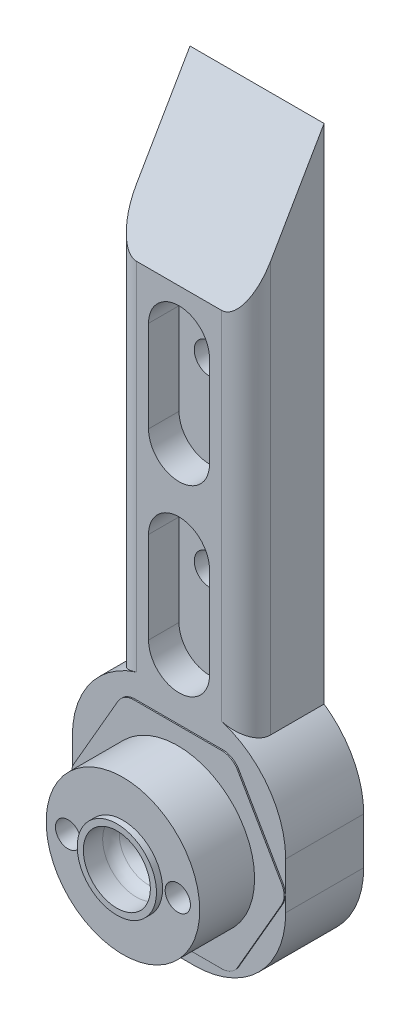
SolidWorks part; units mm, degrees
ref_plane "前视基准面" through (0, 0, 0) normal (0, 0, 1) x (1, 0, 0)
ref_plane "上视基准面" through (0, 0, 0) normal (0, 1, 0) x (1, 0, 0)
ref_plane "右视基准面" through (0, 0, 0) normal (1, 0, 0) x (0, 0, -1)
sketch "草图1" plane through (0, 0, 0) normal (0, 0, 1) x (1, 0, 0)
  circle A0 centre (0, 0) radius 12.6
  dimension "D1" = 25.2
extrude "凸台-拉伸1" add sketch "草图1" along normal blind 9
sketch "草图2" plane through (0, 0, 0) normal (0, 0, -1) x (-1, 0, 0)
  circle A0 centre (0, 0) radius 15
  dimension "D1" = 30
extrude "凸台-拉伸2" add sketch "草图2" along normal blind 5
sketch "草图3" plane through (0, 0, 9) normal (0, 0, 1) x (1, 0, 0)
  circle A0 centre (0, 0) radius 5.5
  dimension "D1" = 11
extrude "切除-拉伸1" cut sketch "草图3" against normal blind 5
sketch "草图4" plane through (0, 0, 9) normal (0, 0, 1) x (1, 0, 0)
  circle A0 centre (-9, 0) radius 2.075
  circle A1 centre (9, 0) radius 2.075
  dimension "D1" = 4.15
  dimension "D2" = 9
  dimension "D3" = 9
extrude "切除-拉伸2" cut sketch "草图4" against normal blind 29
sketch "草图5" plane through (0, 0, 4) normal (0, 0, 1) x (1, 0, 0)
  circle A0 centre (0, 0) radius 3.5
  dimension "D1" = 7
extrude "切除-拉伸3" cut sketch "草图5" against normal blind 31
fillet "圆角1" radius 3 1 edges at (5.5, 0, 4)
fillet "圆角2" radius 5 1 edges at (3.5, 0, 4)
sketch "草图6" plane through (0, 0, 9) normal (0, 0, 1) x (1, 0, 0)
  circle A0 centre (0, 0) radius 5.5
  dimension "D1" = 11
extrude "拉伸-薄壁1" add sketch "草图6" along normal blind 1 thin thin type one direction wall 1
sketch "草图7" plane through (0, 0, -5) normal (0, 0, -1) x (-1, 0, 0)
  line L1 (-8.9489, 15.5) -> (-17.8979, 0)
  line L2 (-17.8979, 0) -> (-8.9489, -15.5)
  line L3 (-8.9489, -15.5) -> (8.9489, -15.5)
  line L4 (8.9489, -15.5) -> (17.8979, 0)
  line L5 (17.8979, 0) -> (8.9489, 15.5)
  line L6 (8.9489, 15.5) -> (-8.9489, 15.5)
  circle A0 centre (0, 0) radius 15.5 construction
  circle A1 centre (0, 0) radius 15
  circle A2 centre (0, 0) radius 15
  dimension "D2" = 31
  dimension "D1" = 0
extrude "凸台-拉伸3" add sketch "草图7" against normal up to surface (5 mm away) up to face at (12.6, 0, 0)
fillet "圆角3" radius 3 6 edges at (17.8979, 0, -2.5) (8.9489, 15.5, -2.5) (-8.9489, 15.5, -2.5) (-17.8979, 0, -2.5) (-8.9489, -15.5, -2.5) (8.9489, -15.5, -2.5)
sketch "草图8" plane through (0, 0, -5) normal (0, 0, -1) x (-1, 0, 0)
  line L6 (-9.815, 14) -> (-17.0318, 1.5)
  line L7 (-17.0318, -1.5) -> (-9.815, -14)
  line L8 (-7.2169, -15.5) -> (7.2169, -15.5)
  line L9 (9.815, -14) -> (17.0318, -1.5)
  line L10 (17.0318, 1.5) -> (9.815, 14)
  line L11 (7.2169, 15.5) -> (-7.2169, 15.5)
  line L12 (-9.815, 14) -> (-17.0318, 1.5)
  line L13 (-17.0318, -1.5) -> (-9.815, -14)
  line L14 (-7.2169, -15.5) -> (7.2169, -15.5)
  line L15 (9.815, -14) -> (17.0318, -1.5)
  line L16 (17.0318, 1.5) -> (9.815, 14)
  line L17 (7.2169, 15.5) -> (-7.2169, 15.5)
  circle A0 centre (0, 0) radius 3.5 construction
  circle A1 centre (0, 0) radius 3.5
  circle A2 centre (-9, 0) radius 4
  circle A3 centre (9, 0) radius 4
  arc A6 (-17.0318, 1.5) -> (-17.0318, -1.5) centre (-14.4338, 0) ccw
  arc A7 (-9.815, -14) -> (-7.2169, -15.5) centre (-7.2169, -12.5) ccw
  arc A8 (7.2169, -15.5) -> (9.815, -14) centre (7.2169, -12.5) ccw
  arc A9 (17.0318, -1.5) -> (17.0318, 1.5) centre (14.4338, 0) ccw
  arc A10 (9.815, 14) -> (7.2169, 15.5) centre (7.2169, 12.5) ccw
  arc A11 (-7.2169, 15.5) -> (-9.815, 14) centre (-7.2169, 12.5) ccw
  arc A12 (-17.0318, 1.5) -> (-17.0318, -1.5) centre (-14.4338, 0) ccw
  arc A13 (-9.815, -14) -> (-7.2169, -15.5) centre (-7.2169, -12.5) ccw
  arc A14 (7.2169, -15.5) -> (9.815, -14) centre (7.2169, -12.5) ccw
  arc A15 (17.0318, -1.5) -> (17.0318, 1.5) centre (14.4338, 0) ccw
  arc A16 (9.815, 14) -> (7.2169, 15.5) centre (7.2169, 12.5) ccw
  arc A17 (-7.2169, 15.5) -> (-9.815, 14) centre (-7.2169, 12.5) ccw
  dimension "D2" = 8
  dimension "D3" = 8
  dimension "D1" = 0
extrude "凸台-拉伸4" add sketch "草图8" along normal blind 8
sketch "草图9" plane through (0, 0, -13) normal (0, 0, -1) x (-1, 0, 0)
  line L1 (-10, 10) -> (10, 10)
  line L2 (-10, 10) -> (-10, -10)
  line L3 (-10, -10) -> (10, -10)
  line L4 (10, 10) -> (10, -10)
  line L5 (-10, 10) -> (10, -10) construction
  line L6 (-10, -10) -> (10, 10) construction
  line L7 (17.5, -17.5) -> (-17.5, -17.5)
  line L8 (17.5, -17.5) -> (17.5, 17.5)
  line L9 (17.5, 17.5) -> (-17.5, 17.5)
  line L10 (-17.5, -17.5) -> (-17.5, 17.5)
  line L11 (17.5, -17.5) -> (-17.5, 17.5) construction
  line L12 (17.5, 17.5) -> (-17.5, -17.5) construction
  point P0 (0, 0)
  point P6 (0, 0)
  dimension "D1" = 20
  dimension "D2" = 20
  dimension "D3" = 35
  dimension "D4" = 35
extrude "凸台-拉伸5" add sketch "草图9" along normal blind 20
sketch "草图10" plane through (0, 0, -13) normal (0, 0, 1) x (1, 0, 0)
  line L4 (17.5, -17.5) -> (17.5, 17.5)
  line L5 (17.5, 17.5) -> (-17.5, 17.5)
  line L6 (-17.5, 17.5) -> (-17.5, -17.5)
  line L7 (-17.5, -17.5) -> (17.5, -17.5)
  line L8 (17.5, -17.5) -> (17.5, 17.5)
  line L9 (17.5, 17.5) -> (-17.5, 17.5)
  line L10 (-17.5, 17.5) -> (-17.5, -17.5)
  line L11 (-17.5, -17.5) -> (17.5, -17.5)
  line L14 (7.2169, 15.5) -> (-7.2169, 15.5)
  line L15 (17.0318, 1.5) -> (9.815, 14)
  line L16 (9.815, -14) -> (17.0318, -1.5)
  line L17 (-7.2169, -15.5) -> (7.2169, -15.5)
  line L18 (-17.0318, -1.5) -> (-9.815, -14)
  line L19 (-9.815, 14) -> (-17.0318, 1.5)
  line L20 (7.2169, 15.5) -> (-7.2169, 15.5)
  line L21 (17.0318, 1.5) -> (9.815, 14)
  line L22 (9.815, -14) -> (17.0318, -1.5)
  line L23 (-7.2169, -15.5) -> (7.2169, -15.5)
  line L24 (-17.0318, -1.5) -> (-9.815, -14)
  line L25 (-9.815, 14) -> (-17.0318, 1.5)
  arc A6 (9.815, 14) -> (7.2169, 15.5) centre (7.2169, 12.5) ccw
  arc A7 (17.0318, -1.5) -> (17.0318, 1.5) centre (14.4338, 0) ccw
  arc A8 (7.2169, -15.5) -> (9.815, -14) centre (7.2169, -12.5) ccw
  arc A9 (-9.815, -14) -> (-7.2169, -15.5) centre (-7.2169, -12.5) ccw
  arc A10 (-17.0318, 1.5) -> (-17.0318, -1.5) centre (-14.4338, 0) ccw
  arc A11 (-7.2169, 15.5) -> (-9.815, 14) centre (-7.2169, 12.5) ccw
  arc A12 (9.815, 14) -> (7.2169, 15.5) centre (7.2169, 12.5) ccw
  arc A13 (17.0318, -1.5) -> (17.0318, 1.5) centre (14.4338, 0) ccw
  arc A14 (7.2169, -15.5) -> (9.815, -14) centre (7.2169, -12.5) ccw
  arc A15 (-9.815, -14) -> (-7.2169, -15.5) centre (-7.2169, -12.5) ccw
  arc A16 (-17.0318, 1.5) -> (-17.0318, -1.5) centre (-14.4338, 0) ccw
  arc A17 (-7.2169, 15.5) -> (-9.815, 14) centre (-7.2169, 12.5) ccw
  dimension "D1" = 0
  dimension "D2" = 0
extrude "凸台-拉伸6" add sketch "草图10" along normal blind 8.5
fillet "圆角4" [suppressed] radius 10
sketch "草图11" plane through (-17.5, 0, 0) normal (-1, 0, 0) x (0, 0, 1)
  line L0 (-33, -17.5) -> (-33, 17.5) construction
  circle A0 centre (-23, 0) radius 2.5
  dimension "D1" = 5
  dimension "D2" = 10
extrude "切除-拉伸4" cut sketch "草图11" against normal blind 15
pattern_circular "阵列(圆周)1" count 4 over 360 about axis through (0, 0, -27) along (0, 0, 1) of "切除-拉伸4"
sketch "草图12" plane through (0, 0, -5) normal (0, 0, -1) x (-1, 0, 0)
  circle A1 centre (9, 0) radius 4
  circle A2 centre (9, 0) radius 4
  circle A3 centre (-9, 0) radius 4
  circle A4 centre (-9, 0) radius 4
  dimension "D1" = 0
  dimension "D2" = 0
extrude "切除-拉伸5" cut sketch "草图12" along normal blind 83
sketch "草图13" plane through (0, 0, -13) normal (0, 0, -1) x (-1, 0, 0)
  line L0 (0, 3.5) -> (0, 10)
  line L1 (10, 10) -> (-10, 10) construction
  line L2 (0, 0) -> (0, 3.5)
  circle A0 centre (0, 0) radius 3.5 construction
extrude "切除-拉伸-薄壁1" [suppressed] cut sketch "草图13" against normal blind 4 thin thin type mid plane wall 4
fillet "圆角5" [suppressed] radius 4
fillet "圆角6" [suppressed] radius 4
fillet "圆角7" [suppressed] radius 3
sketch "草图14" plane through (0, 0, -13) normal (0, 0, -1) x (-1, 0, 0)
  line L0 (-10, -10) -> (10, -10) construction
  line L1 (10, 10) -> (33.2128, 10)
  line L2 (10, 10) -> (10, -10)
  line L3 (10, -10) -> (33.2128, -10)
  line L4 (33.2128, 10) -> (33.2128, -10)
extrude "切除-拉伸6" cut sketch "草图14" along normal blind 41
sketch "草图15" plane through (0, 0, -4.5) normal (0, 0, 1) x (1, 0, 0)
  line L4 (17.5, 17.5) -> (-17.5, 17.5)
  line L5 (-17.5, 17.5) -> (-17.5, -17.5)
  line L6 (-17.5, -17.5) -> (17.5, -17.5)
  line L7 (17.5, -17.5) -> (17.5, 17.5)
  line L8 (17.5, 17.5) -> (-17.5, 17.5)
  line L9 (-17.5, 17.5) -> (-17.5, -17.5)
  line L10 (-17.5, -17.5) -> (17.5, -17.5)
  line L11 (17.5, -17.5) -> (17.5, 17.5)
  line L14 (9.815, -14) -> (17.0318, -1.5)
  line L15 (17.0318, 1.5) -> (9.815, 14)
  line L16 (7.2169, 15.5) -> (-7.2169, 15.5)
  line L17 (-9.815, 14) -> (-17.0318, 1.5)
  line L18 (-17.0318, -1.5) -> (-9.815, -14)
  line L19 (-7.2169, -15.5) -> (7.2169, -15.5)
  line L20 (9.815, -14) -> (17.0318, -1.5)
  line L21 (17.0318, 1.5) -> (9.815, 14)
  line L22 (7.2169, 15.5) -> (-7.2169, 15.5)
  line L23 (-9.815, 14) -> (-17.0318, 1.5)
  line L24 (-17.0318, -1.5) -> (-9.815, -14)
  line L25 (-7.2169, -15.5) -> (7.2169, -15.5)
  arc A14 (17.0318, -1.5) -> (17.0318, 1.5) centre (14.4338, 0) ccw
  arc A15 (9.815, 14) -> (7.2169, 15.5) centre (7.2169, 12.5) ccw
  arc A16 (-7.2169, 15.5) -> (-9.815, 14) centre (-7.2169, 12.5) ccw
  arc A17 (-17.0318, 1.5) -> (-17.0318, -1.5) centre (-14.4338, 0) ccw
  arc A18 (-9.815, -14) -> (-7.2169, -15.5) centre (-7.2169, -12.5) ccw
  arc A19 (7.2169, -15.5) -> (9.815, -14) centre (7.2169, -12.5) ccw
  arc A20 (17.0318, -1.5) -> (17.0318, 1.5) centre (14.4338, 0) ccw
  arc A21 (9.815, 14) -> (7.2169, 15.5) centre (7.2169, 12.5) ccw
  arc A22 (-7.2169, 15.5) -> (-9.815, 14) centre (-7.2169, 12.5) ccw
  arc A23 (-17.0318, 1.5) -> (-17.0318, -1.5) centre (-14.4338, 0) ccw
  arc A24 (-9.815, -14) -> (-7.2169, -15.5) centre (-7.2169, -12.5) ccw
  arc A25 (7.2169, -15.5) -> (9.815, -14) centre (7.2169, -12.5) ccw
  dimension "D1" = 0
  dimension "D2" = 0
extrude "凸台-拉伸7" add sketch "草图15" along normal blind 1.3
sketch "草图16" plane through (0, 0, -13) normal (0, 0, -1) x (-1, 0, 0)
  line L1 (0, 3.5) -> (-9.9868, 3.5)
  line L2 (0, 3.5) -> (0, -3.5)
  line L3 (0, -3.5) -> (-9.9868, -3.5)
  line L4 (-9.9868, 3.5) -> (-9.9868, -3.5)
  circle A0 centre (0, 0) radius 3.5 construction
  dimension "D1" = 7
extrude "切除-拉伸7" [suppressed] cut sketch "草图16" against normal blind 3
sketch "草图18" [suppressed] plane through (0, 0, -13) normal (0, 0, -1) x (-1, 0, 0)
  line L0 (17.1825, 10) -> (-10, 10) construction
  line L1 (7.5, 17.5) -> (30.5, 17.5)
  line L2 (7.5, 17.5) -> (7.5, 10)
  line L3 (7.5, 10) -> (30.5, 10)
  line L4 (30.5, 17.5) -> (30.5, 10)
  dimension "D1" = 7.5
  dimension "D2" = 23
extrude "凸台-拉伸8" [suppressed] add sketch "草图18" along normal blind 20
sketch "草图19" [suppressed] plane through (0, 17.5, 0) normal (0, 1, 0) x (1, 0, 0)
  line L0 (-30.5, 33) -> (7.5, 33) construction
  line L1 (-30.5, 33) -> (-30.5, 13) construction
  circle A0 centre (-22.5, 23) radius 2.55
  dimension "D1" = 5.1
  dimension "D2" = 10
  dimension "D3" = 8
extrude "切除-拉伸8" [suppressed] cut sketch "草图19" against normal blind 20
mirror "镜向1" [suppressed] about plane through (0, 0, 0) normal (0, 1, 0)
fillet "圆角8" [suppressed] radius 3
fillet "圆角9" [suppressed] radius 3
sketch "草图20" plane through (0, 0, -13) normal (0, 0, -1) x (-1, 0, 0)
  line L1 (-25.3768, 23.6724) -> (25.3768, 23.6724)
  line L2 (-25.3768, 23.6724) -> (-25.3768, -23.6724)
  line L3 (-25.3768, -23.6724) -> (25.3768, -23.6724)
  line L4 (25.3768, 23.6724) -> (25.3768, -23.6724)
  line L5 (-25.3768, 23.6724) -> (25.3768, -23.6724) construction
  line L6 (-25.3768, -23.6724) -> (25.3768, 23.6724) construction
  point P0 (0, 0)
extrude "切除-拉伸9" cut sketch "草图20" along normal blind 46
sketch "草图21" plane through (0, 0, -13) normal (0, 0, -1) x (-1, 0, 0)
  line L1 (-17.5, 17.5) -> (17.5, 17.5)
  line L2 (-17.5, 17.5) -> (-17.5, 80)
  line L3 (-17.5, 80) -> (17.5, 80)
  line L4 (17.5, 17.5) -> (17.5, 80)
  dimension "D1" = 35
  dimension "D2" = 62.5
extrude "凸台-拉伸9" add sketch "草图21" against normal up to surface (9.8 mm away) up to face at (0, 0, -3.2)
sketch "草图22" plane through (0, 0, -3.2) normal (0, 0, 1) x (1, 0, 0)
  line L4 (-17.5, 80) -> (-17.5, -17.5)
  line L5 (-17.5, -17.5) -> (17.5, -17.5)
  line L6 (17.5, -17.5) -> (17.5, 80)
  line L7 (17.5, 80) -> (-17.5, 80)
  line L8 (-17.5, 80) -> (-17.5, -17.5)
  line L9 (-17.5, -17.5) -> (17.5, -17.5)
  line L10 (17.5, -17.5) -> (17.5, 80)
  line L11 (17.5, 80) -> (-17.5, 80)
  line L14 (9.815, -14) -> (17.0318, -1.5)
  line L15 (17.0318, 1.5) -> (9.815, 14)
  line L16 (7.2169, 15.5) -> (-7.2169, 15.5)
  line L17 (-9.815, 14) -> (-17.0318, 1.5)
  line L18 (-17.0318, -1.5) -> (-9.815, -14)
  line L19 (-7.2169, -15.5) -> (7.2169, -15.5)
  line L20 (9.815, -14) -> (17.0318, -1.5)
  line L21 (17.0318, 1.5) -> (9.815, 14)
  line L22 (7.2169, 15.5) -> (-7.2169, 15.5)
  line L23 (-9.815, 14) -> (-17.0318, 1.5)
  line L24 (-17.0318, -1.5) -> (-9.815, -14)
  line L25 (-7.2169, -15.5) -> (7.2169, -15.5)
  arc A6 (17.0318, -1.5) -> (17.0318, 1.5) centre (14.4338, 0) ccw
  arc A7 (9.815, 14) -> (7.2169, 15.5) centre (7.2169, 12.5) ccw
  arc A8 (-7.2169, 15.5) -> (-9.815, 14) centre (-7.2169, 12.5) ccw
  arc A9 (-17.0318, 1.5) -> (-17.0318, -1.5) centre (-14.4338, 0) ccw
  arc A10 (-9.815, -14) -> (-7.2169, -15.5) centre (-7.2169, -12.5) ccw
  arc A11 (7.2169, -15.5) -> (9.815, -14) centre (7.2169, -12.5) ccw
  arc A12 (17.0318, -1.5) -> (17.0318, 1.5) centre (14.4338, 0) ccw
  arc A13 (9.815, 14) -> (7.2169, 15.5) centre (7.2169, 12.5) ccw
  arc A14 (-7.2169, 15.5) -> (-9.815, 14) centre (-7.2169, 12.5) ccw
  arc A15 (-17.0318, 1.5) -> (-17.0318, -1.5) centre (-14.4338, 0) ccw
  arc A16 (-9.815, -14) -> (-7.2169, -15.5) centre (-7.2169, -12.5) ccw
  arc A17 (7.2169, -15.5) -> (9.815, -14) centre (7.2169, -12.5) ccw
  dimension "D1" = 0
  dimension "D2" = 0
extrude "凸台-拉伸10" add sketch "草图22" along normal offset from surface (3 mm away) 0.2 up to face at (12.6, 0, 0)
sketch "草图23" plane through (0, 0, -13) normal (0, 0, -1) x (-1, 0, 0)
  line L0 (-17.5, -17.5) -> (17.5, -17.5) construction
  line L1 (-17.5, 80) -> (-11, 80)
  line L2 (-17.5, 80) -> (-17.5, 17.5)
  line L3 (-17.5, 17.5) -> (-11, 17.5)
  line L4 (-11, 80) -> (-11, 17.5)
  line L5 (17.5, 80) -> (11, 80)
  line L6 (17.5, 80) -> (17.5, 17.5)
  line L7 (17.5, 17.5) -> (11, 17.5)
  line L8 (11, 80) -> (11, 17.5)
  dimension "D1" = 22
  dimension "D2" = 35
  dimension "D3" = 35
extrude "切除-拉伸10" cut sketch "草图23" against normal blind 43
fillet "圆角10" radius 15 2 edges at (17.5, -17.5, -6.6) (-17.5, -17.5, -6.6)
fillet "圆角11" radius 15 2 edges at (17.5, 17.5, -6.6) (-17.5, 17.5, -6.6)
sketch "草图24" plane through (0, 0, -0.2) normal (0, 0, 1) x (1, 0, 0)
  line L0 (0, 70) -> (0, 55) construction
  line L1 (5, 70) -> (5, 55)
  line L2 (-5, 70) -> (-5, 55)
  line L3 (0, 40) -> (0, 25) construction
  line L4 (5, 40) -> (5, 25)
  line L5 (-5, 40) -> (-5, 25)
  line L6 (-11, 80) -> (11, 80) construction
  arc A0 (5, 70) -> (-5, 70) centre (0, 70) ccw
  arc A1 (-5, 55) -> (5, 55) centre (0, 55) ccw
  arc A2 (5, 40) -> (-5, 40) centre (0, 40) ccw
  arc A3 (-5, 25) -> (5, 25) centre (0, 25) ccw
  point P3 (0, 62.5)
  point P8 (0, 32.5)
  dimension "D2" = 5
  dimension "D3" = 5
  dimension "D5" = 10
  dimension "D6" = 15
  dimension "D1" = 15
  dimension "D4" = 15
extrude "切除-拉伸11" cut sketch "草图24" against normal blind 5
sketch "草图25" plane through (0, 0, -5.2) normal (0, 0, 1) x (1, 0, 0)
  line L0 (11, 17.5) -> (11, 80) construction
  line L1 (5, 55) -> (5, 70) construction
  line L2 (-11, 80) -> (11, 80) construction
  circle A0 centre (0, 65) radius 2.5
  circle A1 centre (0, 35) radius 2.5
  dimension "D1" = 11
  dimension "D2" = 5
  dimension "D3" = 15
  dimension "D4" = 5
  dimension "D5" = 5
  dimension "D6" = 11
  dimension "D7" = 30
extrude "切除-拉伸12" cut sketch "草图25" against normal blind 33
sketch "草图26" plane through (0, 80, 0) normal (0, 1, 0) x (1, 0, 0)
  line L4 (11, 0.2) -> (11, 13)
  line L5 (11, 13) -> (-11, 13)
  line L6 (-11, 13) -> (-11, 0.2)
  line L7 (-11, 0.2) -> (11, 0.2)
  line L8 (11, 0.2) -> (11, 13)
  line L9 (11, 13) -> (-11, 13)
  line L10 (-11, 13) -> (-11, 0.2)
  line L11 (-11, 0.2) -> (11, 0.2)
  dimension "D1" = 0
extrude "凸台-拉伸11" add sketch "草图26" along normal blind 20
sketch "草图27" plane through (-11, 0, 0) normal (-1, 0, 0) x (0, 0, 1)
  line L0 (-13, 100) -> (-0.2, 77.8297)
  line L1 (-0.2, 100) -> (-0.2, 17.5) construction
  line L2 (-0.2, 77.8297) -> (-0.2, 100)
  line L3 (-0.2, 100) -> (-13, 100)
  dimension "D1" = 30
extrude "切除-拉伸13" cut sketch "草图27" against normal up to vertex (22 mm away) up to point (11, 17.5, -0.2)
sketch "草图28" plane through (0, 0, -13) normal (0, 0, -1) x (-1, 0, 0)
  line L0 (7, 90) -> (7, 10)
  line L1 (11, 100) -> (11, 17.5) construction
  line L2 (-11, 100) -> (11, 100) construction
  dimension "D1" = 4
  dimension "D2" = 10
  dimension "D3" = 80
sweep "切除-扫描1" cut path "草图28" circular profile diameter 6 parameters "D3"=6
fillet "圆角13" radius 3 1 edges at (-7, 10, -10)
fillet "圆角14" radius 3 1 edges at (-7, 90, -10)
fillet "圆角15" radius 4 2 edges at (-11, 47.6649, -0.2) (11, 47.6649, -0.2)
mirror "镜向2" [suppressed] of bodies 134
